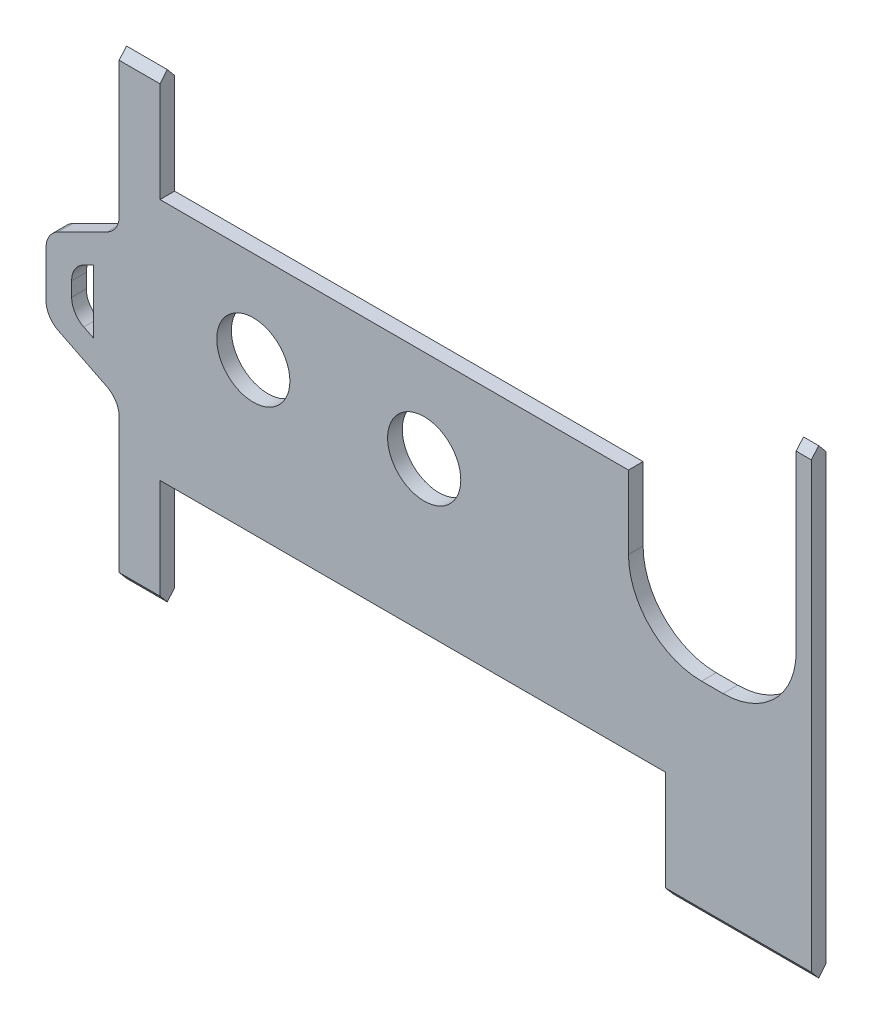
SolidWorks part; units mm, degrees
ref_plane "Front Plane" through (0, 0, 0) normal (0, 0, 1) x (1, 0, 0)
ref_plane "Top Plane" through (0, 0, 0) normal (0, 1, 0) x (1, 0, 0)
ref_plane "Right Plane" through (0, 0, 0) normal (1, 0, 0) x (0, 0, -1)
sketch "Sketch1" plane through (0, 0, 11.1483) normal (0, 0, 1) x (1, 0, 0)
  line L0 (22.423, 106.8975) -> (12.423, 101.8975)
  line L5 (22.223, 125.272) -> (22.223, 68.523) construction
  line L10 (12.423, 101.8975) -> (12.423, 91.8975)
  line L11 (117.248, 128.723) -> (22.223, 128.723) construction
  line L12 (117.248, 128.723) -> (117.248, 65.072) construction
  line L13 (117.248, 65.072) -> (22.223, 65.072) construction
  line L14 (22.223, 128.723) -> (22.223, 65.072) construction
  line L15 (117.048, 128.523) -> (22.423, 128.523)
  line L16 (22.423, 128.523) -> (22.423, 65.272)
  line L17 (117.048, 65.272) -> (22.423, 65.272)
  line L18 (117.048, 128.523) -> (117.048, 65.272)
  line L19 (12.423, 91.8975) -> (22.423, 86.8975)
  line L20 (92.048, 128.523) -> (92.048, 93.523)
  line L21 (92.048, 93.523) -> (117.048, 93.523)
  line L22 (114.9758, 128.523) -> (114.9758, 93.523)
  line L25 (22.423, 106.8975) -> (22.423, 86.8975)
  line L26 (15.923, 94.0606) -> (18.923, 92.5606)
  line L27 (18.923, 101.2344) -> (18.923, 92.5606)
  line L28 (18.923, 101.2344) -> (15.923, 99.7344)
  line L29 (15.923, 99.7344) -> (15.923, 94.0606)
  line L30 (-882.952, 96.8975) -> (49117.048, 96.8975) construction
  line L31 (28.0044, 130.223) -> (28.0044, 127.223) construction
  line L32 (28.0044, 128.523) -> (97.123, 128.523)
  line L33 (28.0044, 128.523) -> (28.0044, 113.523)
  line L34 (28.0044, 113.523) -> (97.123, 113.523)
  line L35 (97.123, 128.523) -> (97.123, 113.523)
  line L37 (97.123, 130.223) -> (97.123, 127.223) construction
  line L38 (28.0044, 80.272) -> (97.123, 80.272)
  line L39 (97.123, 65.272) -> (97.123, 80.272)
  line L40 (28.0044, 65.272) -> (97.123, 65.272)
  line L41 (28.0044, 65.272) -> (28.0044, 80.272)
  circle A0 centre (40.7588, 100.907) radius 5
  circle A1 centre (64.1228, 100.8815) radius 5
  point P4 (22.423, 96.8975)
  point P8 (12.423, 96.8975)
  point P34 (117.048, 96.8975)
  dimension "D7" = 10
  dimension "D8" = 10
  dimension "D1" = 0.2
  dimension "D2" = 10
  dimension "D3" = 10
  dimension "D4" = 20
  dimension "D5" = 35
  dimension "D6" = 25
  dimension "D9" = 3.5
  dimension "D10" = 15
  dimension "D11" = 6.5
extrude "Boss-Extrude1" add sketch "Sketch1" along normal mid plane 2 contours L18 L15 L16 L17 | L10 L19 L16 L0 | L15 L22 L21 L18 region at (22.1994, 96.8975, 11.1483) region at (66.0201, 93.1247, 11.1483) region at (116.0119, 111.023, 11.1483)
sketch "Sketch2" plane through (22.423, 0, 0) normal (-1, 0, 0) x (0, 0, 1)
  line L5 (-986.1517, 96.8975) -> (49013.8483, 96.8975) construction
  line L6 (13.8483, 68.523) -> (13.8483, 125.272) construction
  line L7 (10.1013, 128.523) -> (10.1013, 127.1682)
  line L8 (12.1953, 127.1682) -> (11.1483, 128.4124)
  line L10 (12.1953, 66.6268) -> (12.1953, 65.272)
  line L11 (12.1953, 65.272) -> (10.1013, 65.272)
  line L12 (11.1483, 65.3826) -> (10.1013, 66.6268)
  line L13 (12.1953, 66.6268) -> (11.1483, 65.3826)
  line L14 (11.1483, 65.3826) -> (10.1013, 66.6268)
  line L15 (12.1953, 66.6268) -> (11.1483, 65.3826)
  line L16 (10.1013, 65.272) -> (10.1013, 66.6268)
  line L17 (12.1483, 65.272) -> (10.1483, 65.272) construction
  line L18 (11.1483, 128.4124) -> (10.1013, 127.1682)
  line L19 (12.1953, 128.523) -> (10.1013, 128.523)
  line L20 (12.1953, 127.1682) -> (12.1953, 128.523)
  point P9 (13.8483, 96.8975)
  dimension "D2" = 0.2
extrude "Cut-Extrude1" cut sketch "Sketch2" against normal through all
fillet "Fillet1" radius 10 2 edges at (92.048, 93.523, 11.1483) (114.9758, 93.523, 11.1483)
fillet "Fillet2" radius 3 6 edges at (15.923, 99.7344, 11.1483) (15.923, 94.0606, 11.1483) (22.423, 106.8975, 11.1483) (12.423, 101.8975, 11.1483) (12.423, 91.8975, 11.1483) (22.423, 86.8975, 11.1483)
